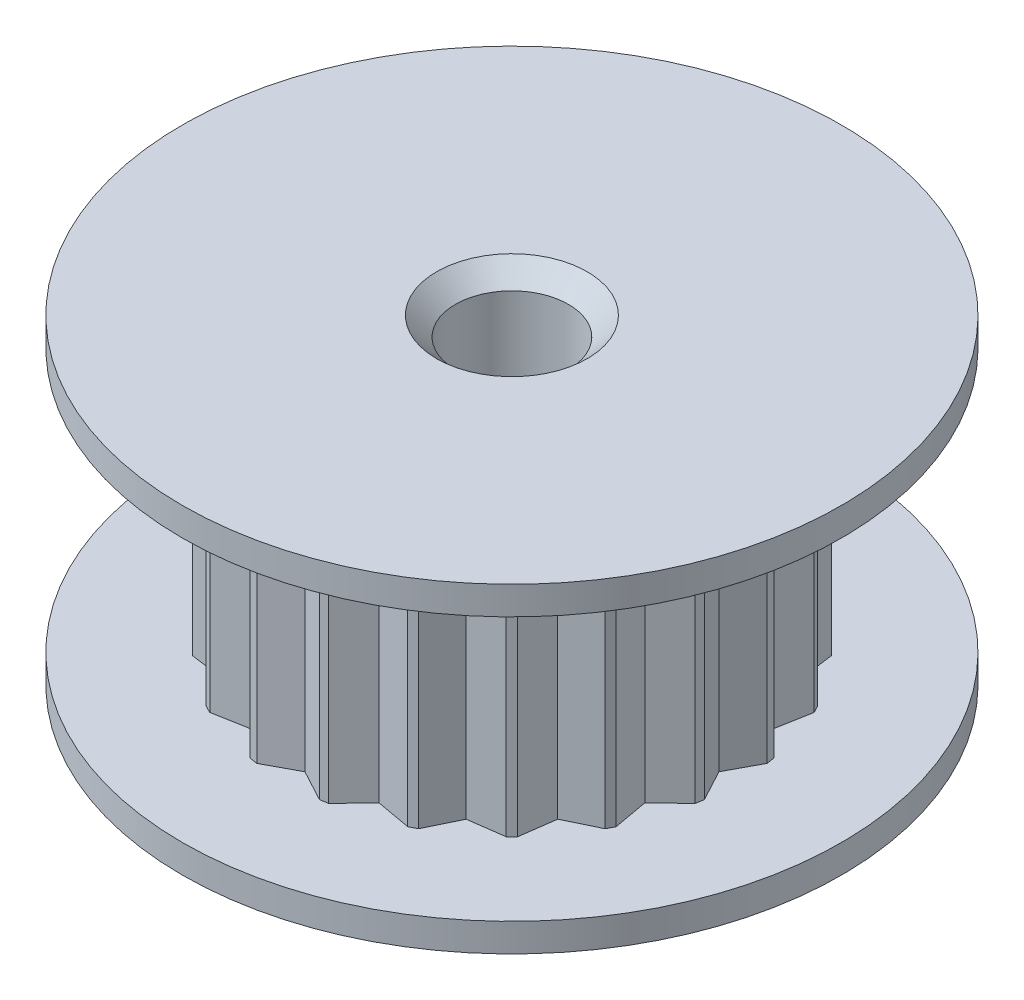
SolidWorks part; units mm, degrees
ref_plane "Front Plane" through (0, 0, 0) normal (0, 0, 1) x (1, 0, 0)
ref_plane "Top Plane" through (0, 0, 0) normal (0, 1, 0) x (1, 0, 0)
ref_plane "Right Plane" through (0, 0, 0) normal (1, 0, 0) x (0, 0, -1)
sketch "Sketch1" plane through (0, 0, 0) normal (0, 1, 0) x (1, 0, 0)
  circle A0 centre (0, 0) radius 8.75
  circle A1 centre (0, 0) radius 1.5
  dimension "D1" = 17.5
  dimension "D2" = 3
extrude "Boss-Extrude1" add sketch "Sketch1" along normal blind 8.5
ref_plane "Плоскость1" through (0, 4.25, 0) normal (0, 1, 0) x (1, 0, 0)
sketch "Sketch2" plane through (0, 8.5, 0) normal (0, 1, 0) x (1, 0, 0)
  circle A0 centre (0, 0) radius 6
  circle A1 centre (0, 0) radius 9
extrude "Cut-Extrude2" cut sketch "Sketch2" against normal blind 3.5 and the other way blind 3.5 from surface starting at plane "Плоскость1"
sketch "Sketch4" plane through (0, 8.5, 0) normal (0, 1, 0) x (1, 0, 0)
  line L0 (0, 0) -> (0, 6) construction
  line L2 (-0.94, 5.4956) -> (-0.94, 6) construction
  line L3 (0, 5.4956) -> (0.94, 5.4956) construction
  line L7 (0, 5.4956) -> (-0.94, 5.4956) construction
  line L8 (0.94, 5.4956) -> (0.94, 6) construction
  line L9 (-0.94, 6) -> (0.94, 6)
  line L10 (0.94, 6) -> (0, 5.4956)
  line L11 (0, 5.4956) -> (-0.94, 6)
  line L12 (1.6982, 5.2267) -> (0.9601, 5.9968)
  line L13 (0.9601, 5.9968) -> (2.7481, 5.4159)
  line L14 (2.7481, 5.4159) -> (1.6982, 5.2267)
  line L15 (3.2303, 4.4461) -> (2.7662, 5.4066)
  line L16 (2.7662, 5.4066) -> (4.2872, 4.3016)
  line L17 (4.2872, 4.3016) -> (3.2303, 4.4461)
  line L18 (4.4461, 3.2303) -> (4.3016, 4.2872)
  line L19 (4.3016, 4.2872) -> (5.4066, 2.7662)
  line L20 (5.4066, 2.7662) -> (4.4461, 3.2303)
  line L21 (5.2267, 1.6982) -> (5.4159, 2.7481)
  line L22 (5.4159, 2.7481) -> (5.9968, 0.9601)
  line L23 (5.9968, 0.9601) -> (5.2267, 1.6982)
  line L24 (5.4956, 0) -> (6, 0.94)
  line L25 (6, 0.94) -> (6, -0.94)
  line L26 (6, -0.94) -> (5.4956, 0)
  line L27 (5.2267, -1.6982) -> (5.9968, -0.9601)
  line L28 (5.9968, -0.9601) -> (5.4159, -2.7481)
  line L29 (5.4159, -2.7481) -> (5.2267, -1.6982)
  line L30 (4.4461, -3.2303) -> (5.4066, -2.7662)
  line L31 (5.4066, -2.7662) -> (4.3016, -4.2872)
  line L32 (4.3016, -4.2872) -> (4.4461, -3.2303)
  line L33 (3.2303, -4.4461) -> (4.2872, -4.3016)
  line L34 (4.2872, -4.3016) -> (2.7662, -5.4066)
  line L35 (2.7662, -5.4066) -> (3.2303, -4.4461)
  line L36 (1.6982, -5.2267) -> (2.7481, -5.4159)
  line L37 (2.7481, -5.4159) -> (0.9601, -5.9968)
  line L38 (0.9601, -5.9968) -> (1.6982, -5.2267)
  line L39 (0, -5.4956) -> (0.94, -6)
  line L40 (0.94, -6) -> (-0.94, -6)
  line L41 (-0.94, -6) -> (0, -5.4956)
  line L42 (-1.6982, -5.2267) -> (-0.9601, -5.9968)
  line L43 (-0.9601, -5.9968) -> (-2.7481, -5.4159)
  line L44 (-2.7481, -5.4159) -> (-1.6982, -5.2267)
  line L45 (-3.2303, -4.4461) -> (-2.7662, -5.4066)
  line L46 (-2.7662, -5.4066) -> (-4.2872, -4.3016)
  line L47 (-4.2872, -4.3016) -> (-3.2303, -4.4461)
  line L48 (-4.4461, -3.2303) -> (-4.3016, -4.2872)
  line L49 (-4.3016, -4.2872) -> (-5.4066, -2.7662)
  line L50 (-5.4066, -2.7662) -> (-4.4461, -3.2303)
  line L51 (-5.2267, -1.6982) -> (-5.4159, -2.7481)
  line L52 (-5.4159, -2.7481) -> (-5.9968, -0.9601)
  line L53 (-5.9968, -0.9601) -> (-5.2267, -1.6982)
  line L54 (-5.4956, 0) -> (-6, -0.94)
  line L55 (-6, -0.94) -> (-6, 0.94)
  line L56 (-6, 0.94) -> (-5.4956, 0)
  line L57 (-5.2267, 1.6982) -> (-5.9968, 0.9601)
  line L58 (-5.9968, 0.9601) -> (-5.4159, 2.7481)
  line L59 (-5.4159, 2.7481) -> (-5.2267, 1.6982)
  line L60 (-4.4461, 3.2303) -> (-5.4066, 2.7662)
  line L61 (-5.4066, 2.7662) -> (-4.3016, 4.2872)
  line L62 (-4.3016, 4.2872) -> (-4.4461, 3.2303)
  line L63 (-3.2303, 4.4461) -> (-4.2872, 4.3016)
  line L64 (-4.2872, 4.3016) -> (-2.7662, 5.4066)
  line L65 (-2.7662, 5.4066) -> (-3.2303, 4.4461)
  line L66 (-1.6982, 5.2267) -> (-2.7481, 5.4159)
  line L67 (-2.7481, 5.4159) -> (-0.9601, 5.9968)
  line L68 (-0.9601, 5.9968) -> (-1.6982, 5.2267)
  circle A0 centre (0, 0) radius 6
  point P69 (0, 0)
  dimension "D1" = 20
extrude "Cut-Extrude5" cut sketch "Sketch4" against normal up to surface (7.75 mm away) from surface contours L17 A0 L15 | L20 A0 L18 | L14 A0 L12 | L10 A0 L11 | L68 A0 L66 | L65 A0 L63 | L62 A0 L60 | L59 A0 L57 | L23 A0 L21 | L26 A0 L24 | L29 A0 L27 | L56 A0 L54 | L50 A0 L48 | L47 A0 L45 | L44 A0 L42 | A0 L39 L41 | L38 A0 L36 | L35 A0 L33 | L32 A0 L30 | L51 L52 L53 region at (0, 8.5, -5.8186) region at (-1.7981, 8.5, -5.5339) region at (1.7981, 8.5, -5.5339) region at (-3.4201, 8.5, -4.7074) region at (3.4201, 8.5, -4.7074) region at (-4.7074, 8.5, -3.4201) region at (4.7074, 8.5, -3.4201) region at (-5.5339, 8.5, -1.7981) region at (5.5339, 8.5, -1.7981) region at (-5.8186, 8.5, 0) region at (5.8186, 8.5, 0) region at (5.5339, 8.5, 1.7981) region at (-4.7074, 8.5, 3.4201) region at (4.7074, 8.5, 3.4201) region at (-3.4201, 8.5, 4.7074) region at (3.4201, 8.5, 4.7074) region at (-1.7981, 8.5, 5.5339) region at (1.7981, 8.5, 5.5339) region at (0, 8.5, 5.8186) up to face at (0, 0.75, 6) starting at face at (0, 7.75, 6)
chamfer "Chamfer1" distance 0.5 angle 45 2 edges at (0, 0, 1.5) (0, 8.5, 1.5)
